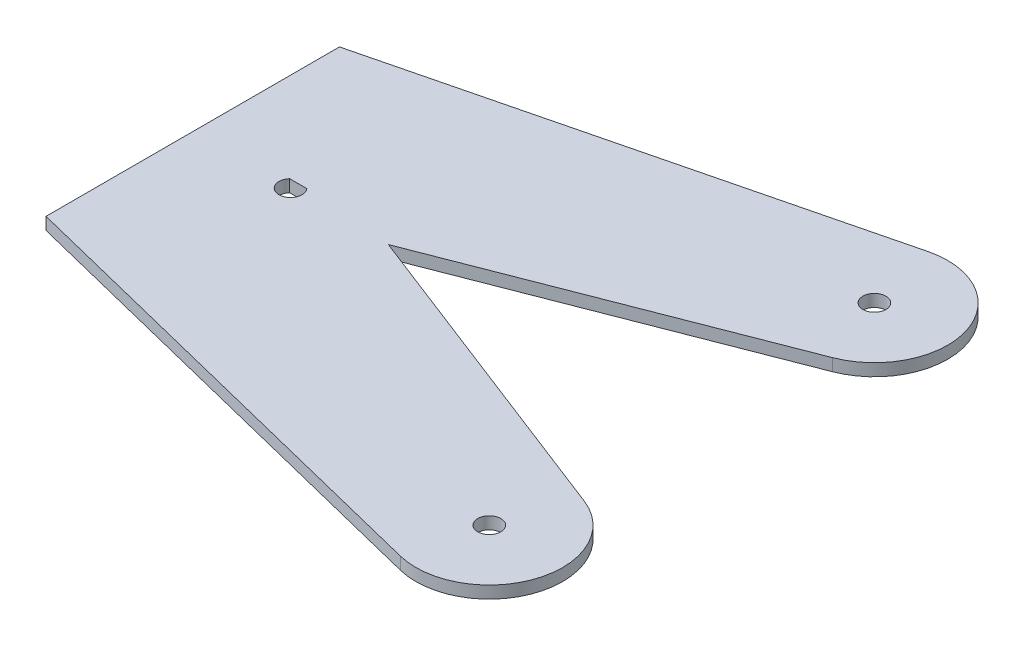
SolidWorks part; units mm, degrees
ref_plane "Front Plane" through (0, 0, 0) normal (0, 0, 1) x (1, 0, 0)
ref_plane "Top Plane" through (0, 0, 0) normal (0, 1, 0) x (1, 0, 0)
ref_plane "Right Plane" through (0, 0, 0) normal (1, 0, 0) x (0, 0, -1)
sketch "Sketch1" plane through (0, 0, 0) normal (0, 1, 0) x (1, 0, 0)
  line L0 (-25.4, 38.1) -> (97.0101, 68.4888)
  line L1 (-25.4, 38.1) -> (-25.4, -38.1)
  line L2 (-25.4, -38.1) -> (97.0101, -68.4888)
  line L3 (108.491, -32.24) -> (25.4, 0)
  line L5 (25.4, 0) -> (108.491, 32.24)
  line L6 (101.6, -50) -> (101.6, 50) construction
  line L7 (-2.2361, 2) -> (2.2361, 2)
  arc A0 (108.491, -32.24) -> (97.0101, -68.4888) centre (101.6, -50) cw
  arc A1 (97.0101, 68.4888) -> (108.491, 32.24) centre (101.6, 50) cw
  arc A2 (2.2361, 2) -> (-2.2361, 2) centre (0, 0) cw
  circle A3 centre (101.6, 50) radius 3
  circle A4 centre (101.6, -50) radius 3
  point P8 (-25.4, 0)
  point P12 (101.6, 0)
  dimension "D1" = 19.05
  dimension "D7" = 3
  dimension "D9" = 6
  dimension "D2" = 76.2
  dimension "D3" = 25.4
  dimension "D4" = 101.6
  dimension "D5" = 100
  dimension "D6" = 25.4
  dimension "D8" = 2
extrude "Boss-Extrude1" add sketch "Sketch1" along normal mid plane 3.175 contours A4 L3 L5 A3 A1 L0 L1 L2 A0 L7 A2 region at (36.2893, 0, -51.3436)
